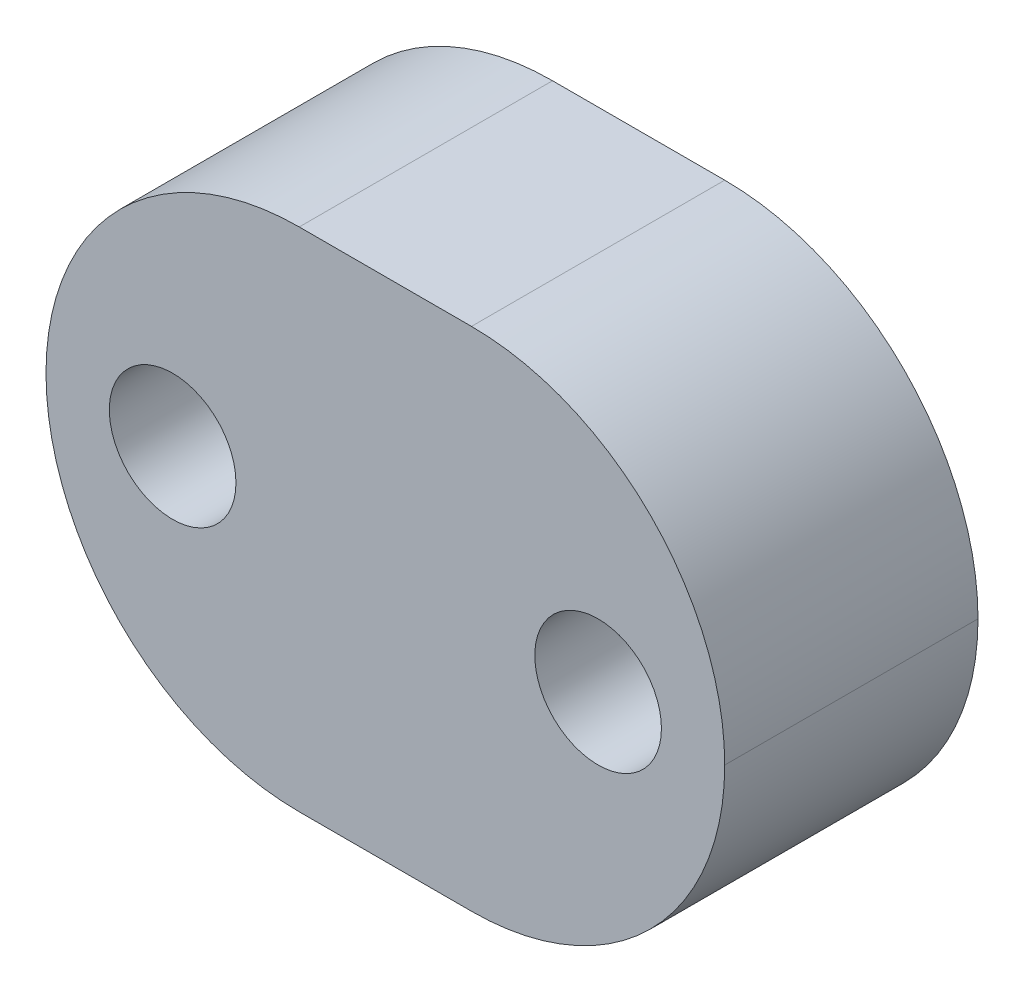
SolidWorks part; units mm, degrees
ref_plane "Front Plane" through (0, 0, 0) normal (0, 0, 1) x (1, 0, 0)
ref_plane "Top Plane" through (0, 0, 0) normal (0, 1, 0) x (1, 0, 0)
ref_plane "Right Plane" through (0, 0, 0) normal (1, 0, 0) x (0, 0, -1)
sketch "Sketch1" plane through (0, 0, 0) normal (0, 0, 1) x (1, 0, 0)
  line L1 (-13.4, 10) -> (13.4, 10)
  line L2 (-13.4, 10) -> (-13.4, -10)
  line L3 (-13.4, -10) -> (13.4, -10)
  line L4 (13.4, 10) -> (13.4, -10)
  line L5 (-13.4, 10) -> (13.4, -10) construction
  line L6 (-13.4, -10) -> (13.4, 10) construction
  circle A0 centre (-8.4, 0) radius 2.5
  circle A1 centre (8.4, 0) radius 2.5
  point P0 (0, 0)
  dimension "D4" = 5
  dimension "D5" = 5
  dimension "D6" = 5
  dimension "D1" = 26.8
  dimension "D2" = 20
  dimension "D3" = 5
extrude "Boss-Extrude1" add sketch "Sketch1" along normal blind 10
fillet "Fillet1" radius 10 4 edges at (13.4, -10, 5) (13.4, 10, 5) (-13.4, -10, 5) (-13.4, 10, 5)
